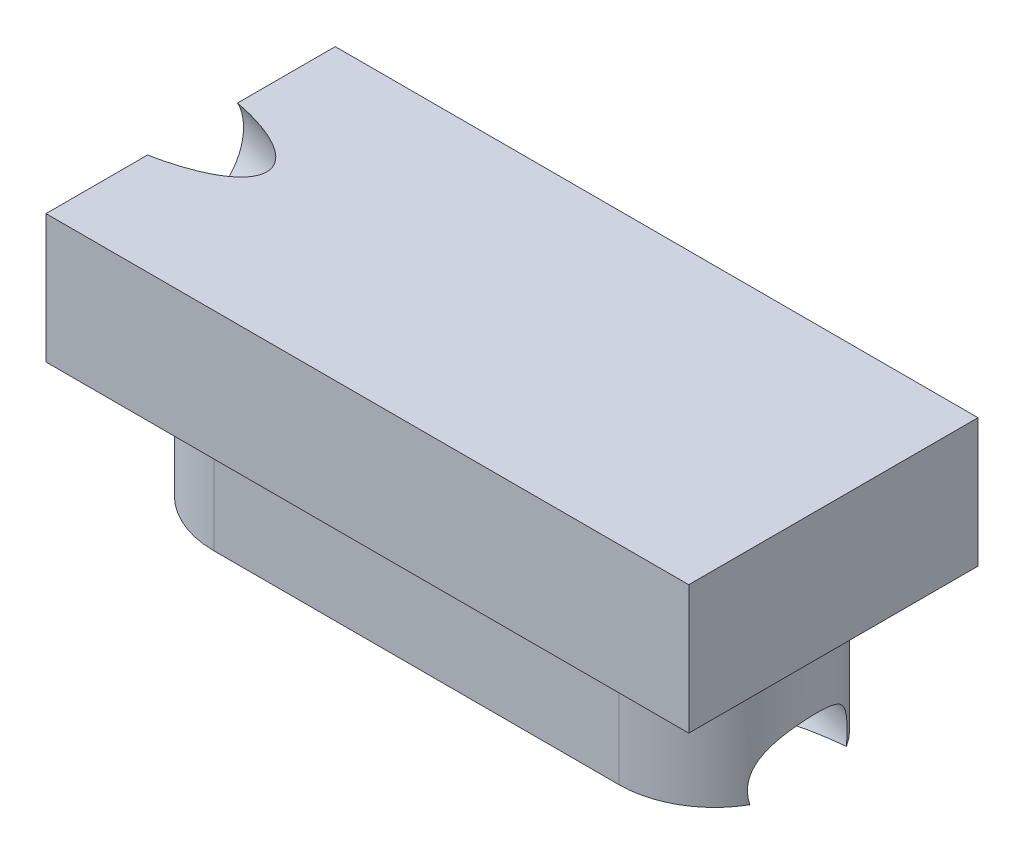
SolidWorks part; units mm, degrees
ref_plane "Front Plane" through (0, 0, 0) normal (0, 0, 1) x (1, 0, 0)
ref_plane "Top Plane" through (0, 0, 0) normal (0, 1, 0) x (1, 0, 0)
ref_plane "Right Plane" through (0, 0, 0) normal (1, 0, 0) x (0, 0, -1)
sketch "Sketch1" plane through (0, 0, 0) normal (0, 1, 0) x (1, 0, 0)
  line L0 (0, 1.3786) -> (0, -1.4577) construction
  line L1 (-1.575, 0.6964) -> (1.575, 0.6964)
  line L2 (-1.575, -0.7911) -> (1.575, -0.7911)
  line L3 (-1.575, -0.7911) -> (-1.575, 0.6964) construction
  line L4 (1.575, 0.6964) -> (1.575, -0.7911) construction
  arc A0 (-1.575, -0.7911) -> (-1.575, 0.6964) centre (-1.575, -0.0474) cw
  arc A1 (1.575, 0.6964) -> (1.575, -0.7911) centre (1.575, -0.0474) cw
  point P8 (0, 0.6964)
  dimension "D3" = 0.7437
  dimension "D2" = 3.15
extrude "Boss-Extrude1" add sketch "Sketch1" along normal blind 1
sketch "Sketch2" [suppressed] plane through (0, 0, 0) normal (0, 0, 1) x (1, 0, 0)
  line L1 (1.575, 0) -> (2.3688, 0) construction
  line L3 (2.3688, 0) -> (-4.5982, 2.5357)
  line L4 (1.575, 0) -> (2.3688, 0) construction
  dimension "D1" = 20
ref_plane "Plane1" [suppressed] through (-1.3856, 1, 0) normal (-1, 0, 0) x (0, 0, 1)
sketch "Sketch5" plane through (0, 1, 0) normal (0, 1, 0) x (1, 0, 0)
  line L0 (0, -0.7911) -> (0, -1.1724) construction
  line L1 (-2.5, 1.0776) -> (2.5, 1.0776)
  line L2 (-2.5, 1.0776) -> (-2.5, -1.1724)
  line L3 (-2.5, -1.1724) -> (2.5, -1.1724)
  line L4 (2.5, 1.0776) -> (2.5, -1.1724)
  line L5 (-1.0372, -0.0474) -> (-2.5, -0.0474) construction
  line L7 (2.5, 1.0776) -> (-2.5, -1.1724) construction
  line L8 (-1.575, -0.7911) -> (1.575, -0.7911) construction
  line L9 (-1.575, 0.6964) -> (1.575, 0.6964) construction
  line L10 (-1.575, -0.7911) -> (1.575, -0.7911) construction
  line L11 (-1.575, 0.6964) -> (1.575, 0.6964) construction
  line L12 (-1.575, -0.7911) -> (1.575, -0.7911) construction
  line L13 (1.575, 0.6964) -> (-1.575, -0.7911) construction
  point P15 (0, -0.0474)
  point P17 (0, -0.0474)
  dimension "D1" = 2.25
  dimension "D2" = 5
extrude "Boss-Extrude2" add sketch "Sketch5" along normal blind 1
sketch "Sketch4" plane through (2.5, 1, 0) normal (-1, 0, 0) x (0, 0, 1)
  line L0 (0.0474, 0) -> (0, -3.1672) construction
  line L1 (1.1724, 0) -> (-1.0776, 0) construction
  circle A0 centre (0.0323, -1.0065) radius 0.3969
  point P3 (0.0323, -1.0065)
  dimension "D1" = 0.7937
sweep "Cut-Sweep3" [suppressed] cut profiles "Sketch4" path "Sketch2"
sketch "Sketch6" plane through (0, 0, 0) normal (0, 0, 1) x (1, 0, 0)
  line L0 (2.5, 0) -> (-2.8676, 1.9537)
  line L1 (1.575, 0) -> (2.3188, 0) construction
  line L2 (1.575, 0) -> (2.3188, 0) construction
  line L3 (2.5, 2) -> (-2.5, 2) construction
  line L4 (2.5, 2) -> (-2.5, 2) construction
  line L5 (2.5, 2) -> (2.5, 0) construction
  dimension "D1" = 20
sweep "Cut-Sweep4" cut profiles "Sketch4<2>" path "Sketch6"
sketch "Sketch4<2>" plane through (2.5, 1, 0) normal (-1, 0, 0) x (0, 0, 1) same geometry as "Sketch4"
